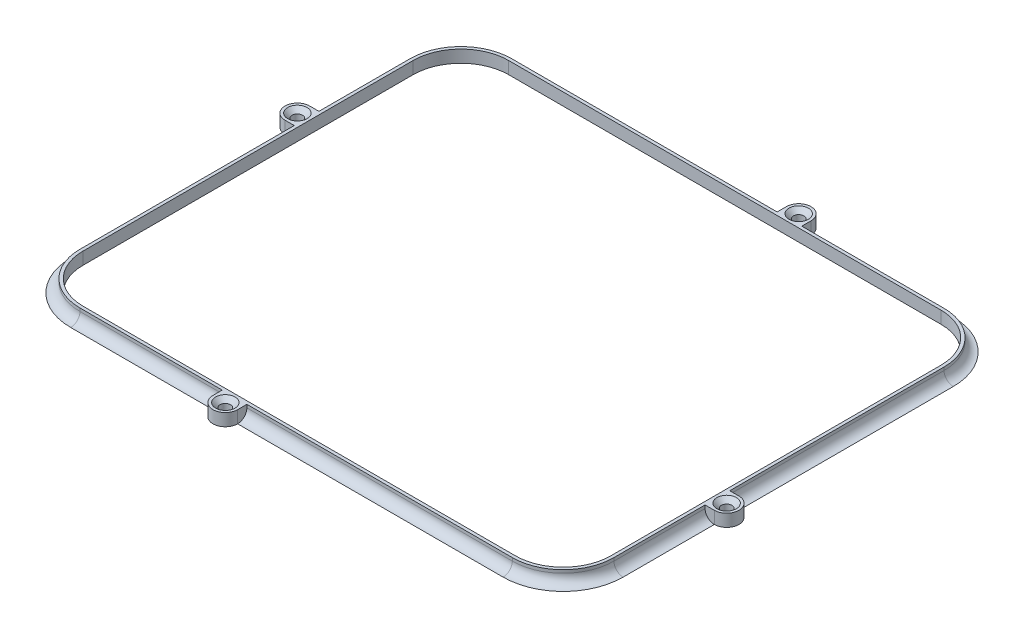
SolidWorks part; units mm, degrees
ref_plane "Front Plane" through (0, 0, 0) normal (0, 0, 1) x (1, 0, 0)
ref_plane "Top Plane" through (0, 0, 0) normal (0, 1, 0) x (1, 0, 0)
ref_plane "Right Plane" through (0, 0, 0) normal (1, 0, 0) x (0, 0, -1)
ref_axis "Axis1" through (0, 55, 0) along (0, -1, 0)
sketch "Sketch1" plane through (0, 0, 0) normal (0, 1, 0) x (1, 0, 0)
  line L0 (86.7, -53.6) -> (86.7, 53.6) construction
  line L1 (70.2, 70.1) -> (-70.2, 70.1) construction
  line L2 (-86.7, 53.6) -> (-86.7, -53.6) construction
  line L3 (-70.2, -70.1) -> (70.2, -70.1) construction
  line L4 (-70.2, -69.1) -> (70.2, -69.1) construction
  line L5 (85.7, -53.6) -> (85.7, 53.6) construction
  line L6 (-85.7, 53.6) -> (-85.7, -53.6) construction
  line L7 (70.2, 69.1) -> (-70.2, 69.1) construction
  line L8 (86.7, -53.6) -> (86.7, 53.6)
  line L9 (70.2, 70.1) -> (-70.2, 70.1)
  line L10 (-86.7, 53.6) -> (-86.7, -53.6)
  line L11 (-70.2, -70.1) -> (70.2, -70.1)
  line L12 (-70.2, -69.1) -> (70.2, -69.1)
  line L13 (85.7, -53.6) -> (85.7, 53.6)
  line L14 (-85.7, 53.6) -> (-85.7, -53.6)
  line L15 (70.2, 69.1) -> (-70.2, 69.1)
  arc A0 (86.7, 53.6) -> (70.2, 70.1) centre (70.2, 53.6) ccw construction
  arc A1 (-70.2, 70.1) -> (-86.7, 53.6) centre (-70.2, 53.6) ccw construction
  arc A2 (-86.7, -53.6) -> (-70.2, -70.1) centre (-70.2, -53.6) ccw construction
  arc A3 (-85.7, -53.6) -> (-70.2, -69.1) centre (-70.2, -53.6) ccw construction
  arc A4 (70.2, -70.1) -> (86.7, -53.6) centre (70.2, -53.6) ccw construction
  arc A5 (70.2, -69.1) -> (85.7, -53.6) centre (70.2, -53.6) ccw construction
  arc A6 (85.7, 53.6) -> (70.2, 69.1) centre (70.2, 53.6) ccw construction
  arc A7 (-70.2, 69.1) -> (-85.7, 53.6) centre (-70.2, 53.6) ccw construction
  arc A8 (86.7, 53.6) -> (70.2, 70.1) centre (70.2, 53.6) ccw
  arc A9 (-70.2, 70.1) -> (-86.7, 53.6) centre (-70.2, 53.6) ccw
  arc A10 (-86.7, -53.6) -> (-70.2, -70.1) centre (-70.2, -53.6) ccw
  arc A11 (-85.7, -53.6) -> (-70.2, -69.1) centre (-70.2, -53.6) ccw
  arc A12 (70.2, -70.1) -> (86.7, -53.6) centre (70.2, -53.6) ccw
  arc A13 (70.2, -69.1) -> (85.7, -53.6) centre (70.2, -53.6) ccw
  arc A14 (85.7, 53.6) -> (70.2, 69.1) centre (70.2, 53.6) ccw
  arc A15 (-70.2, 69.1) -> (-85.7, 53.6) centre (-70.2, 53.6) ccw
extrude "Boss-Extrude1" add sketch "Sketch1" along normal blind 4
sketch "Sketch4" plane through (0, 0, 0) normal (0, 0, 1) x (1, 0, 0)
  line L0 (-86.7, 0) -> (-89.7, 0)
  line L1 (-86.7, 0) -> (-86.7, 3)
  arc A0 (-89.7, 0) -> (-86.7, 3) centre (-89.7, 3) ccw
  dimension "D1" = 3
sketch "Sketch5" plane through (0, 0, 0) normal (0, -1, 0) x (1, 0, 0)
  line L0 (86.7, 53.6) -> (86.7, -53.6) construction
  line L1 (70.2, -70.1) -> (-70.2, -70.1) construction
  line L2 (-86.7, -53.6) -> (-86.7, 53.6) construction
  line L3 (-70.2, 70.1) -> (70.2, 70.1) construction
  line L4 (86.7, 53.6) -> (86.7, -53.6)
  line L5 (70.2, -70.1) -> (-70.2, -70.1)
  line L6 (-86.7, -53.6) -> (-86.7, 53.6)
  line L7 (-70.2, 70.1) -> (70.2, 70.1)
  arc A0 (86.7, 53.6) -> (70.2, 70.1) centre (70.2, 53.6) ccw construction
  arc A1 (70.2, -70.1) -> (86.7, -53.6) centre (70.2, -53.6) ccw construction
  arc A2 (-86.7, -53.6) -> (-70.2, -70.1) centre (-70.2, -53.6) ccw construction
  arc A3 (-70.2, 70.1) -> (-86.7, 53.6) centre (-70.2, 53.6) ccw construction
  arc A4 (86.7, 53.6) -> (70.2, 70.1) centre (70.2, 53.6) ccw
  arc A5 (70.2, -70.1) -> (86.7, -53.6) centre (70.2, -53.6) ccw
  arc A6 (-86.7, -53.6) -> (-70.2, -70.1) centre (-70.2, -53.6) ccw
  arc A7 (-70.2, 70.1) -> (-86.7, 53.6) centre (-70.2, 53.6) ccw
sweep "Sweep1" add profiles "Sketch4" path "Sketch5"
sketch "Sketch2" plane through (0, 0, 0) normal (0, 1, 0) x (1, 0, 0)
  line L0 (-86.7, 24) -> (-89.7, 24)
  line L1 (-86.7, 53.6) -> (-86.7, -53.6) construction
  line L2 (-86.7, 16) -> (-89.7, 16)
  line L3 (-86.7, 24) -> (-86.7, 16)
  line L4 (16, 70.1) -> (16, 73.1)
  line L5 (70.2, 70.1) -> (-70.2, 70.1) construction
  line L6 (24, 70.1) -> (24, 73.1)
  line L7 (16, 70.1) -> (24, 70.1)
  line L8 (0, 0) -> (20, 0) construction
  line L9 (20, 0) -> (20, 73.1) construction
  line L16 (-89.7, 20) -> (0, 20) construction
  line L17 (0, 20) -> (0, 0) construction
  line L18 (-24, -70.1) -> (-24, -73.1)
  line L19 (-16, -70.1) -> (-24, -70.1)
  line L20 (-16, -70.1) -> (-16, -73.1)
  line L21 (86.7, -24) -> (89.7, -24)
  line L22 (86.7, -24) -> (86.7, -16)
  line L23 (86.7, -16) -> (89.7, -16)
  arc A0 (-89.7, 24) -> (-89.7, 16) centre (-89.7, 20) ccw
  circle A1 centre (-89.7, 20) radius 1.6
  arc A2 (16, 73.1) -> (24, 73.1) centre (20, 73.1) cw
  circle A3 centre (20, 73.1) radius 1.6
  arc A8 (-16, -73.1) -> (-24, -73.1) centre (-20, -73.1) cw
  circle A9 centre (-20, -73.1) radius 1.6
  arc A10 (89.7, -24) -> (89.7, -16) centre (89.7, -20) ccw
  circle A11 centre (89.7, -20) radius 1.6
  point P27 (0, 0)
  point P35 (0, 0)
  dimension "D1" = 3.2
  dimension "D3" = 8
  dimension "D2" = 3
  dimension "D4" = 20
  dimension "D5" = 20
  dimension "D6" = 2
  dimension "D7" = 2
extrude "Boss-Extrude2" add sketch "Sketch2" along normal through all
hole_wizard "CSK for M3 Flat Head Machine Screw1" positions "3DSketch1" profile "Sketch3" countersink size "M3" standard "ANSI Metric" end condition through all
sketch3d "3DSketch1"
  line L0 (-89.7, 4, -20) -> (-89.7, 0, -20) construction
  line L1 (-89.7, 4, -20) -> (-89.7, 0, -20) construction
  line L3 (20, 4, -73.1) -> (20, 0, -73.1) construction
  line L4 (20, 4, -73.1) -> (20, 0, -73.1) construction
  line L7 (89.7, 4, 20) -> (89.7, 0, 20) construction
  line L8 (-20, 4, 73.1) -> (-20, 0, 73.1) construction
  point P0 (-89.7, 4, -20)
  point P7 (-89.7, 4, -20)
  point P9 (-89.7, 4, -20)
  point P11 (-89.7, 4, -20)
  point P13 (-89.7, 4, -20)
  point P17 (89.7, 4, 20)
  point P21 (20, 4, -73.1)
  point P27 (-20, 4, 73.1)
  point P34 (20, 4, -73.1)
  point P39 (20, 4, -73.1)
  point P49 (20, 4, -73.1)
  point P51 (20, 4, -73.1)
  point P59 (89.7, 4, 0)
  point P60 (0, 0, 0)
  point P61 (89.7, 4, 20)
  point P64 (0, 0, 0)
  point P65 (0, 4, 73.1)
  point P66 (0, 0, 0)
  point P67 (-3.8738, 4, 74.9313)
  point P68 (0, 0, 0)
  point P69 (0, 0, 0)
  point P70 (-20, 4, 73.1)
  point P73 (0, 0, 0)
  point P74 (0, 0, 0)
sketch "Sketch3" plane through (20, 4, -73.1) normal (1, 0, 0) x (0, 0, 1)
  line L0 (0, 0) -> (0, 4.0013)
  line L1 (0, 4.0013) -> (1.7, 4.0013)
  line L2 (1.7, 4.0013) -> (1.7, 1.45)
  line L3 (1.7, 1.45) -> (3.15, 0)
  line L5 (3.15, 0) -> (0, 0)
  line L6 (-1.7, 1.45) -> (-3.15, 0) construction
  line L11 (0, -6.35) -> (0, 107.95) construction
  dimension "Thru Hole Dia." = 3.4
  dimension "Thru Hole Depth" = 4.0013
  dimension "Near C'Sink Dia." = 6.3
  dimension "Near C'Sink Angle" = 90
